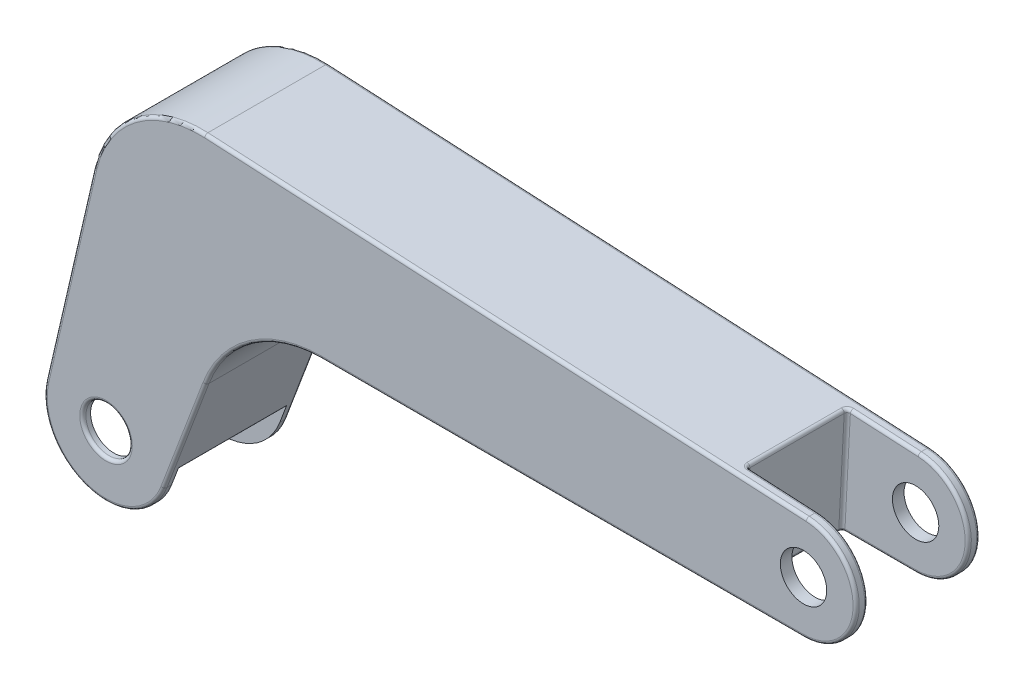
SolidWorks part; units mm, degrees
ref_plane "Ön Düzlem" through (0, 0, 0) normal (0, 0, 1) x (1, 0, 0)
ref_plane "Üst Düzlem" through (0, 0, 0) normal (0, 1, 0) x (1, 0, 0)
ref_plane "Sağ Düzlem" through (0, 0, 0) normal (1, 0, 0) x (0, 0, -1)
sketch "Çizim1" plane through (0, 0, 0) normal (0, 0, 1) x (1, 0, 0)
  line L0 (-225.0615, -160.2364) -> (-178.27, -36.573)
  line L1 (-178.27, -36.573) -> (222.806, -36.573)
  line L2 (222.806, -36.573) -> (222.806, 29.798)
  line L3 (222.806, 29.798) -> (-257.194, 54.9243)
  line L4 (-301.4511, -137.097) -> (-257.194, 54.9243)
  circle A0 centre (-262.473, -146.0807) radius 40
  dimension "D1" = 80
  dimension "D2" = 192.0213
  dimension "D3" = 99.982
  dimension "D4" = 480
extrude "Yükseklik-Ekstrüzyon1" add sketch "Çizim1" along normal blind 80 contours A0 L0 L1 L2 L3 L4 region at (-68.7627, -9.9901, 0)
extrude "Yükseklik-Ekstrüzyon2" add sketch "Çizim1<3>" along normal blind 5 contours A0 region at (-262.473, -146.0807, 0)
sketch "Çizim1<3>" plane through (0, 0, 0) normal (0, 0, 1) x (1, 0, 0) same geometry as "Çizim1"
extrude "Yükseklik-Ekstrüzyon3" add sketch "Çizim1<4>" along normal blind 5 from offset 75 contours A0
sketch "Çizim1<4>" plane through (0, 0, 0) normal (0, 0, 1) x (1, 0, 0) same geometry as "Çizim1"
fillet "Radyus1" radius 80 1 edges at (-178.27, -36.573, 40)
fillet "Radyus2" radius 70 1 edges at (-257.194, 54.9243, 40)
fillet "Radyus3" 2 edges at (222.806, 29.798, 40) (222.806, -36.573, 40) type full round first side face at (12.1435, 40.8254, 40) second side face at (49.9005, -36.573, 40) middle face at (222.806, -3.3875, 40)
sketch "Çizim2" plane through (0, 0, 80) normal (0, 0, 1) x (1, 0, 0)
  circle A0 centre (-262.473, -146.0807) radius 15
extrude "Kes-Ekstrüzyon1" cut sketch "Çizim2" against normal blind 107
fillet "Radyus4" radius 1 1 edges at (-301.4511, -137.097, 40)
fillet "Radyus5" radius 1 1 edges at (-225.0615, -160.2364, 40)
fillet "Radyus6" radius 2 18 edges at (-244.3173, 37.844, 0) (-285.9205, -69.7135, 0) (-274.0692, -184.3629, 0) (-211.4447, -124.249, 0) (-168.4752, -50.7516, 0) (32.8738, -36.573, 0) (222.7944, -3.4099, 0) (-3.9932, 41.6701, 0) (-247.473, -146.0807, 0) (-168.4752, -50.7516, 80) (-211.4447, -124.249, 80) (-274.0692, -184.3629, 80) (-285.9205, -69.7135, 80) (-244.3173, 37.844, 80) (-3.9932, 41.6701, 80) (222.7944, -3.4099, 80) (32.8738, -36.573, 80) (-247.473, -146.0807, 80)
sketch "Çizim3" plane through (2.1644, 41.3478, 0) normal (0.0523, 0.9986, 0) x (0.9986, -0.0523, 0)
  line L0 (222.6797, -78) -> (222.6797, -2) construction
  line L1 (302.6797, -72.5) -> (142.6797, -72.5)
  line L2 (302.6797, -72.5) -> (302.6797, -7.5)
  line L3 (302.6797, -7.5) -> (142.6797, -7.5)
  line L4 (142.6797, -72.5) -> (142.6797, -7.5)
  line L5 (302.6797, -72.5) -> (142.6797, -7.5) construction
  line L6 (302.6797, -7.5) -> (142.6797, -72.5) construction
  point P0 (222.6797, -40)
  dimension "D1" = 65
  dimension "D2" = 80
extrude "Kes-Ekstrüzyon2" cut sketch "Çizim3" against normal blind 107
fillet "Radyus7" radius 2 10 edges at (140.9605, -36.573, 40) (164.8565, -36.573, 7.5) (164.8565, -36.573, 72.5) (222.7944, -3.4099, 7.5) (222.7944, -3.4099, 72.5) (167.5908, 32.6883, 7.5) (167.5908, 32.6883, 72.5) (144.649, 33.8892, 40) (142.8048, -1.3419, 72.5) (142.8048, -1.3419, 7.5)
sketch "Çizim4" plane through (0, 0, 80) normal (0, 0, 1) x (1, 0, 0)
  circle A0 centre (188.7526, -2.5195) radius 15
  dimension "D1" = 30
extrude "Kes-Ekstrüzyon3" cut sketch "Çizim4" against normal blind 107
